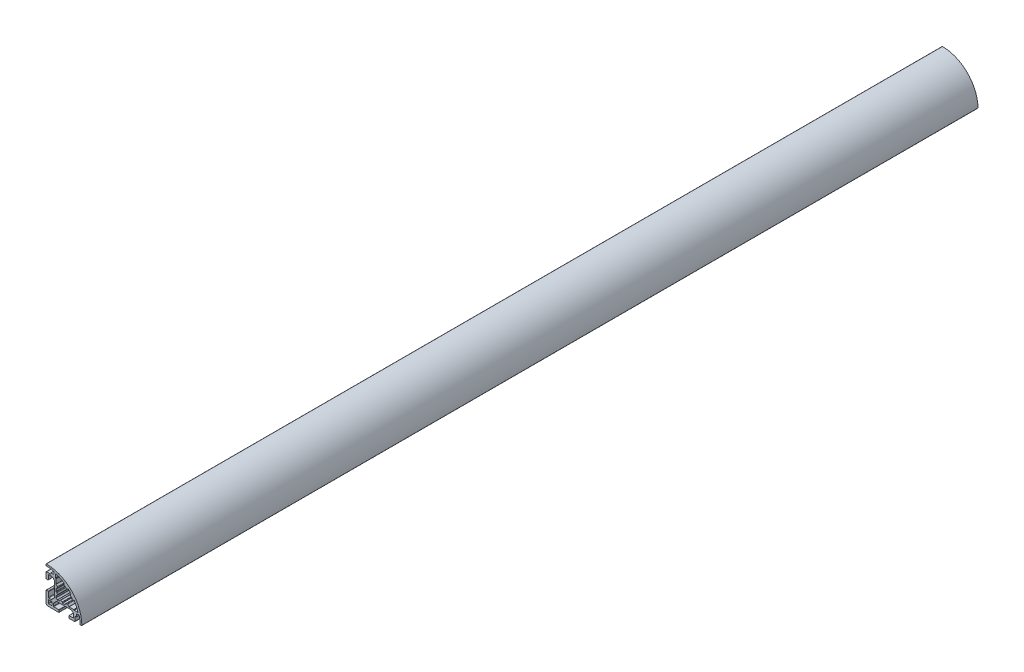
SolidWorks part; units mm, degrees
ref_plane "Plano frontal" through (0, 0, 0) normal (0, 0, 1) x (1, 0, 0)
ref_plane "Plano superior" through (0, 0, 0) normal (0, 1, 0) x (1, 0, 0)
ref_plane "Plano direito" through (0, 0, 0) normal (1, 0, 0) x (0, 0, -1)
ref_plane "Plano1" through (0, 0, 0) normal (0, 0, -1) x (-1, 0, 0)
sketch "Esboço1" plane through (0, 0, 0) normal (0, 0, -1) x (-1, 0, 0)
  line L0 (12.7, -13) -> (10.3, -13)
  line L1 (10, -12.7) -> (10, -10.3)
  line L2 (10.3, -10) -> (12.7, -10)
  line L3 (13, -10.3) -> (13, -12.7)
  line L4 (-0.95, 6.7) -> (-0.3, 6.7)
  line L5 (0, 7) -> (0, 8.4776)
  line L6 (7, 11.4273) -> (7, 8.6799)
  line L7 (6.9121, 8.4678) -> (6.7879, 8.3435)
  line L8 (6.7, 8.1314) -> (6.7, 4.3494)
  line L9 (6.6121, 4.1372) -> (5.4871, 3.0123)
  line L10 (6.1579, 1.25) -> (6.4, 1.25)
  line L11 (6.7, 0.95) -> (6.7, -0.95)
  line L12 (6.4, -1.25) -> (6.1579, -1.25)
  line L13 (5.4871, -3.0123) -> (6.6121, -4.1372)
  line L14 (6.7, -4.3494) -> (6.7, -5.4396)
  line L15 (6.6121, -5.6517) -> (5.6517, -6.6121)
  line L16 (5.4395, -6.7) -> (4.3494, -6.7)
  line L17 (4.1373, -6.6121) -> (3.0123, -5.4871)
  line L18 (1.25, -6.1579) -> (1.25, -6.4)
  line L19 (0.95, -6.7) -> (-0.95, -6.7)
  line L20 (-1.25, -6.4) -> (-1.25, -6.1579)
  line L21 (-3.0123, -5.4871) -> (-4.1373, -6.6121)
  line L22 (-4.3494, -6.7) -> (-8.1314, -6.7)
  line L23 (-8.3435, -6.7879) -> (-8.4678, -6.9121)
  line L24 (-8.6799, -7) -> (-11.4273, -7)
  line L25 (-8.4777, 0) -> (-7, 0)
  line L26 (-6.7, 0.3) -> (-6.7, 0.95)
  line L27 (-6.4, 1.25) -> (-6.1579, 1.25)
  line L28 (-5.4871, 3.0123) -> (-5.7974, 3.3226)
  line L29 (-3.3226, 5.7974) -> (-3.0123, 5.4871)
  line L30 (-1.25, 6.1579) -> (-1.25, 6.4)
  line L31 (7.9882, 6.432) -> (8.7045, 7.072)
  line L32 (8.7045, 7.072) -> (8.7283, 7.4958)
  line L33 (8.7283, 7.4958) -> (9.1516, 7.472)
  line L34 (9.1516, 7.472) -> (9.8678, 8.112)
  line L35 (10.08, 8.1999) -> (12.7001, 8.1998)
  line L36 (13.0001, 7.8998) -> (13, 4.3499)
  line L37 (13.3, 4.0499) -> (14.7, 4.0498)
  line L38 (15, 4.3498) -> (15, 8.8999)
  line L39 (14.5, 9.3999) -> (11.3, 9.3999)
  line L40 (11, 9.6999) -> (11, 10.1999)
  line L41 (10.7, 10.4999) -> (8.8, 10.4999)
  line L42 (8.5, 10.7999) -> (8.5, 12.51)
  line L43 (15, 13.7984) -> (15, 14.6985)
  line L44 (-14.6985, -15) -> (-13.7984, -15)
  line L45 (-12.5105, -8.5) -> (-10.8005, -8.5)
  line L46 (-10.5005, -8.8) -> (-10.5005, -10.7)
  line L47 (-10.2005, -11) -> (-9.7004, -11)
  line L48 (-9.4004, -11.3) -> (-9.4004, -14.5)
  line L49 (-8.9004, -15) -> (-4.3504, -15)
  line L50 (-4.0504, -14.7) -> (-4.0504, -13.3)
  line L51 (-4.3504, -13) -> (-7.9004, -12.9999)
  line L52 (-8.2004, -12.6999) -> (-8.2004, -10.0799)
  line L53 (-8.1125, -9.8677) -> (-7.4725, -9.1515)
  line L54 (-7.4725, -9.1515) -> (-7.4963, -8.728)
  line L55 (-7.4963, -8.728) -> (-7.0727, -8.7042)
  line L56 (-7.0727, -8.7042) -> (-6.4326, -7.988)
  line L57 (-6.2205, -7.9001) -> (6.2197, -7.9001)
  line L58 (6.4318, -7.988) -> (8.7117, -10.4679)
  line L59 (8.7996, -10.6801) -> (8.7996, -12.7001)
  line L60 (8.4996, -13.0001) -> (4.3496, -13.0001)
  line L61 (4.0496, -13.3001) -> (4.0496, -14.7)
  line L62 (4.3496, -15) -> (13.5, -15)
  line L63 (15, -13.5) -> (15, -4.3503)
  line L64 (14.7, -4.0503) -> (13.2999, -4.0503)
  line L65 (12.9999, -4.3503) -> (12.9999, -8.5003)
  line L66 (12.6999, -8.8003) -> (10.6798, -8.8003)
  line L67 (10.4677, -8.7124) -> (7.9878, -6.4325)
  line L68 (7.9003, -6.2203) -> (7.9003, 6.2198)
  arc A0 (10.3, -13) -> (10, -12.7) centre (10.3, -12.7) cw
  arc A1 (10, -10.3) -> (10.3, -10) centre (10.3, -10.3) cw
  arc A2 (12.7, -10) -> (13, -10.3) centre (12.7, -10.3) cw
  arc A3 (13, -12.7) -> (12.7, -13) centre (12.7, -12.7) cw
  arc A4 (-0.3, 6.7) -> (0, 7) centre (-0.3, 7) ccw
  arc A5 (0, 8.4776) -> (0.1408, 8.7319) centre (0.3, 8.4776) cw
  arc A6 (0.1408, 8.7319) -> (6.6101, 11.7135) centre (15, -15) cw
  arc A7 (6.6101, 11.7135) -> (7, 11.4273) centre (6.7, 11.4273) cw
  arc A8 (7, 8.6799) -> (6.9121, 8.4678) centre (6.7, 8.6799) cw
  arc A9 (6.7879, 8.3435) -> (6.7, 8.1314) centre (7, 8.1314) ccw
  arc A10 (6.7, 4.3494) -> (6.6121, 4.1372) centre (6.4, 4.3494) cw
  arc A11 (5.4871, 3.0123) -> (5.43, 2.6678) centre (5.6993, 2.8001) ccw
  arc A12 (5.43, 2.6678) -> (5.867, 1.4768) centre (0, 0) cw
  arc A13 (5.867, 1.4768) -> (6.1579, 1.25) centre (6.1579, 1.55) ccw
  arc A14 (6.4, 1.25) -> (6.7, 0.95) centre (6.4, 0.95) cw
  arc A15 (6.7, -0.95) -> (6.4, -1.25) centre (6.4, -0.95) cw
  arc A16 (6.1579, -1.25) -> (5.867, -1.4768) centre (6.1579, -1.55) ccw
  arc A17 (5.867, -1.4768) -> (5.43, -2.6678) centre (0, 0) cw
  arc A18 (5.43, -2.6678) -> (5.4871, -3.0123) centre (5.6993, -2.8001) ccw
  arc A19 (6.6121, -4.1372) -> (6.7, -4.3494) centre (6.4, -4.3494) cw
  arc A20 (6.7, -5.4396) -> (6.6121, -5.6517) centre (6.4, -5.4396) cw
  arc A21 (5.6517, -6.6121) -> (5.4395, -6.7) centre (5.4395, -6.4) cw
  arc A22 (4.3494, -6.7) -> (4.1373, -6.6121) centre (4.3494, -6.4) cw
  arc A23 (3.0123, -5.4871) -> (2.6678, -5.43) centre (2.8001, -5.6993) ccw
  arc A24 (2.6678, -5.43) -> (1.4768, -5.867) centre (0, 0) cw
  arc A25 (1.4768, -5.867) -> (1.25, -6.1579) centre (1.55, -6.1579) ccw
  arc A26 (1.25, -6.4) -> (0.95, -6.7) centre (0.95, -6.4) cw
  arc A27 (-0.95, -6.7) -> (-1.25, -6.4) centre (-0.95, -6.4) cw
  arc A28 (-1.25, -6.1579) -> (-1.4768, -5.867) centre (-1.55, -6.1579) ccw
  arc A29 (-1.4768, -5.867) -> (-2.6678, -5.43) centre (0, 0) cw
  arc A30 (-2.6678, -5.43) -> (-3.0123, -5.4871) centre (-2.8001, -5.6993) ccw
  arc A31 (-4.1373, -6.6121) -> (-4.3494, -6.7) centre (-4.3494, -6.4) cw
  arc A32 (-8.1314, -6.7) -> (-8.3435, -6.7879) centre (-8.1314, -7) ccw
  arc A33 (-8.4678, -6.9121) -> (-8.6799, -7) centre (-8.6799, -6.7) cw
  arc A34 (-11.4273, -7) -> (-11.7135, -6.6101) centre (-11.4273, -6.7) cw
  arc A35 (-11.7135, -6.6101) -> (-8.7319, -0.1408) centre (15, -15) cw
  arc A36 (-8.7319, -0.1408) -> (-8.4777, 0) centre (-8.4777, -0.3) cw
  arc A37 (-7, 0) -> (-6.7, 0.3) centre (-7, 0.3) ccw
  arc A38 (-6.7, 0.95) -> (-6.4, 1.25) centre (-6.4, 0.95) cw
  arc A39 (-6.1579, 1.25) -> (-5.867, 1.4768) centre (-6.1579, 1.55) ccw
  arc A40 (-5.867, 1.4768) -> (-5.43, 2.6678) centre (0, 0) cw
  arc A41 (-5.43, 2.6678) -> (-5.4871, 3.0123) centre (-5.6993, 2.8001) ccw
  arc A42 (-5.7974, 3.3226) -> (-5.8083, 3.7354) centre (-5.5853, 3.5347) cw
  arc A43 (-5.8083, 3.7354) -> (-3.7354, 5.8083) centre (15, -15) cw
  arc A44 (-3.7354, 5.8083) -> (-3.3226, 5.7974) centre (-3.5347, 5.5853) cw
  arc A45 (-3.0123, 5.4871) -> (-2.6678, 5.43) centre (-2.8001, 5.6993) ccw
  arc A46 (-2.6678, 5.43) -> (-1.4768, 5.867) centre (0, 0) cw
  arc A47 (-1.4768, 5.867) -> (-1.25, 6.1579) centre (-1.55, 6.1579) ccw
  arc A48 (-1.25, 6.4) -> (-0.95, 6.7) centre (-0.95, 6.4) cw
  arc A49 (9.8678, 8.112) -> (10.08, 8.1999) centre (10.08, 7.8999) cw
  arc A50 (12.7001, 8.1998) -> (13.0001, 7.8998) centre (12.7001, 7.8998) cw
  arc A51 (13, 4.3499) -> (13.3, 4.0499) centre (13.3, 4.3499) ccw
  arc A52 (14.7, 4.0498) -> (15, 4.3498) centre (14.7, 4.3498) ccw
  arc A53 (15, 8.8999) -> (14.5, 9.3999) centre (14.5, 8.8999) ccw
  arc A54 (11.3, 9.3999) -> (11, 9.6999) centre (11.3, 9.6999) cw
  arc A55 (11, 10.1999) -> (10.7, 10.4999) centre (10.7, 10.1999) ccw
  arc A56 (8.8, 10.4999) -> (8.5, 10.7999) centre (8.8, 10.7999) cw
  arc A57 (8.5, 12.51) -> (8.734, 12.8026) centre (8.8, 12.51) cw
  arc A58 (8.734, 12.8026) -> (14.7031, 13.4984) centre (15, -15) cw
  arc A59 (14.7031, 13.4984) -> (15, 13.7984) centre (14.7, 13.7984) ccw
  arc A60 (15, 14.6985) -> (14.697, 14.9985) centre (14.7, 14.6985) ccw
  arc A61 (14.697, 14.9985) -> (-14.9985, -14.697) centre (15, -15) ccw
  arc A62 (-14.9985, -14.697) -> (-14.6985, -15) centre (-14.6985, -14.7) ccw
  arc A63 (-13.7984, -15) -> (-13.4985, -14.7031) centre (-13.7984, -14.7) ccw
  arc A64 (-13.4985, -14.7031) -> (-12.8027, -8.734) centre (15, -15) cw
  arc A65 (-12.8027, -8.734) -> (-12.5105, -8.5) centre (-12.51, -8.8) cw
  arc A66 (-10.8005, -8.5) -> (-10.5005, -8.8) centre (-10.8005, -8.8) cw
  arc A67 (-10.5005, -10.7) -> (-10.2005, -11) centre (-10.2005, -10.7) ccw
  arc A68 (-9.7004, -11) -> (-9.4004, -11.3) centre (-9.7004, -11.3) cw
  arc A69 (-9.4004, -14.5) -> (-8.9004, -15) centre (-8.9004, -14.5) ccw
  arc A70 (-4.3504, -15) -> (-4.0504, -14.7) centre (-4.3504, -14.7) ccw
  arc A71 (-4.0504, -13.3) -> (-4.3504, -13) centre (-4.3504, -13.3) ccw
  arc A72 (-7.9004, -12.9999) -> (-8.2004, -12.6999) centre (-7.9004, -12.6999) cw
  arc A73 (-8.2004, -10.0799) -> (-8.1125, -9.8677) centre (-7.9004, -10.0799) cw
  arc A74 (-6.4326, -7.988) -> (-6.2205, -7.9001) centre (-6.2205, -8.2001) cw
  arc A75 (6.2197, -7.9001) -> (6.4318, -7.988) centre (6.2197, -8.2001) cw
  arc A76 (8.7117, -10.4679) -> (8.7996, -10.6801) centre (8.4996, -10.6801) cw
  arc A77 (8.7996, -12.7001) -> (8.4996, -13.0001) centre (8.4996, -12.7001) cw
  arc A78 (4.3496, -13.0001) -> (4.0496, -13.3001) centre (4.3496, -13.3001) ccw
  arc A79 (4.0496, -14.7) -> (4.3496, -15) centre (4.3496, -14.7) ccw
  arc A80 (13.5, -15) -> (15, -13.5) centre (13.5, -13.5) ccw
  arc A81 (15, -4.3503) -> (14.7, -4.0503) centre (14.7, -4.3503) ccw
  arc A82 (13.2999, -4.0503) -> (12.9999, -4.3503) centre (13.2999, -4.3503) ccw
  arc A83 (12.9999, -8.5003) -> (12.6999, -8.8003) centre (12.6999, -8.5003) cw
  arc A84 (10.6798, -8.8003) -> (10.4677, -8.7124) centre (10.6798, -8.5003) cw
  arc A85 (7.9878, -6.4325) -> (7.9003, -6.2203) centre (8.2003, -6.2208) cw
  arc A86 (7.9003, 6.2198) -> (7.9882, 6.432) centre (8.2003, 6.2198) cw
  dimension "D1" = 1.5
  dimension "D2" = 30
extrude "Ressalto-extrusão1" add sketch "Esboço1" against normal blind 750
